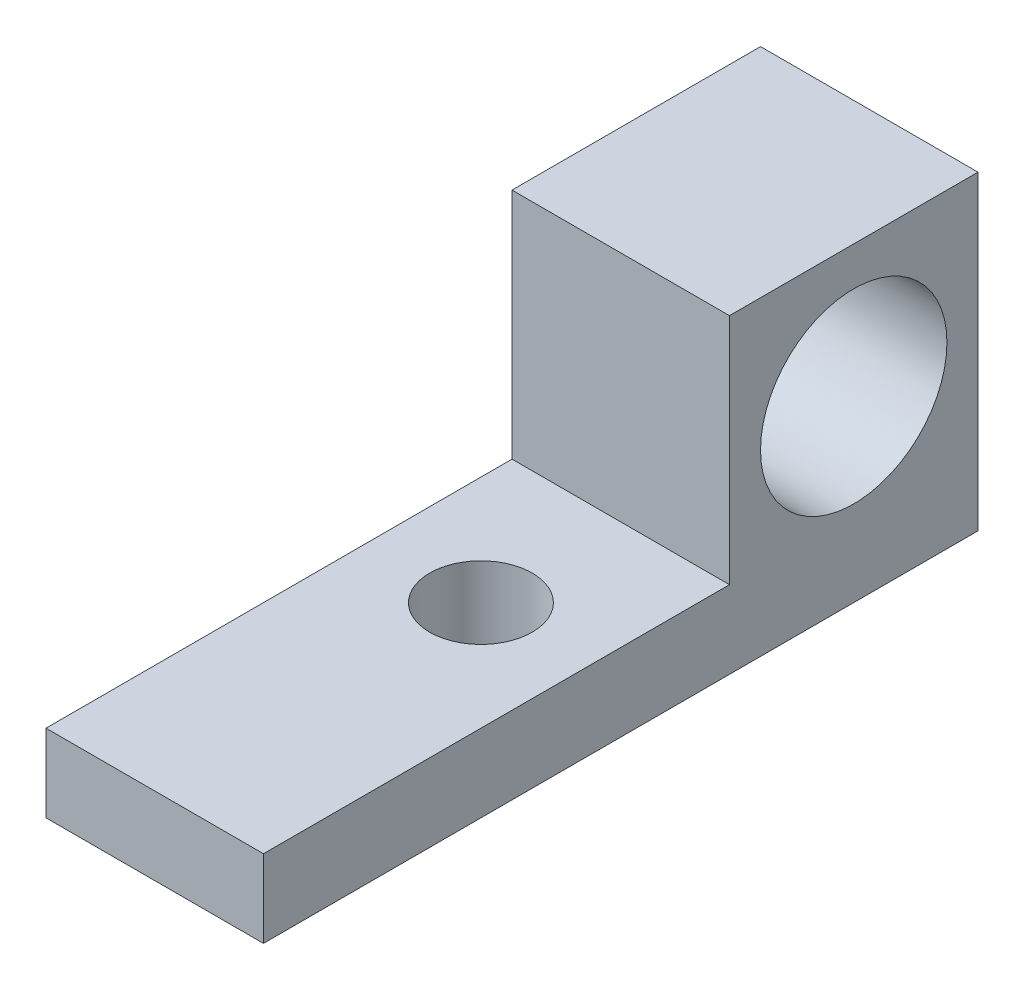
SolidWorks part; units mm, degrees
material "6061-T6 (SS)"
ref_plane "Front Plane" through (0, 0, 0) normal (0, 0, 1) x (1, 0, 0)
ref_plane "Top Plane" through (0, 0, 0) normal (0, 1, 0) x (1, 0, 0)
ref_plane "Right Plane" through (0, 0, 0) normal (1, 0, 0) x (0, 0, -1)
sketch "Sketch1" plane through (0, 0, 0) normal (1, 0, 0) x (0, 0, -1)
  line L0 (0, 0) -> (46, 0)
  line L1 (46, 0) -> (46, 20)
  line L2 (46, 20) -> (30, 20)
  line L3 (30, 20) -> (30, 5)
  line L4 (30, 5) -> (0, 5)
  line L5 (0, 5) -> (0, 0)
  line L6 (38, 20) -> (38, 0) construction
  circle A0 centre (38, 11.5) radius 6
  dimension "D4" = 12
  dimension "D1" = 20
  dimension "D2" = 16
  dimension "D3" = 46
  dimension "D5" = 11.5
  dimension "D6" = 5
extrude "Boss-Extrude1" add sketch "Sketch1" along normal blind 14
hole_wizard "M6 Clearance Hole1" positions "Sketch3" profile "Sketch2" hole size "M6" standard "ISO" end condition up to next
sketch "Sketch3" plane through (0, 5, 0) normal (0, 1, 0) x (-1, 0, 0)
  line L0 (-7, 0) -> (-7, -30) construction
  line L1 (-14, 0) -> (0, 0) construction
  line L2 (-14, -30) -> (0, -30) construction
  line L3 (-14, -46) -> (0, -46) construction
  point P0 (-7, -21)
  dimension "D1" = 25
sketch "Sketch2" plane through (7, 5, -21) normal (1, 0, 0) x (0, 0, 1)
  line L0 (0, 0) -> (0, 5)
  line L1 (0, 5) -> (3.3, 5)
  line L2 (3.3, 5) -> (3.3, 0)
  line L5 (3.3, 0) -> (0, 0)
  line L11 (0, -6.35) -> (0, 107.95) construction
  dimension "Thru Hole Dia." = 6.6
  dimension "Thru Hole Depth" = 5
